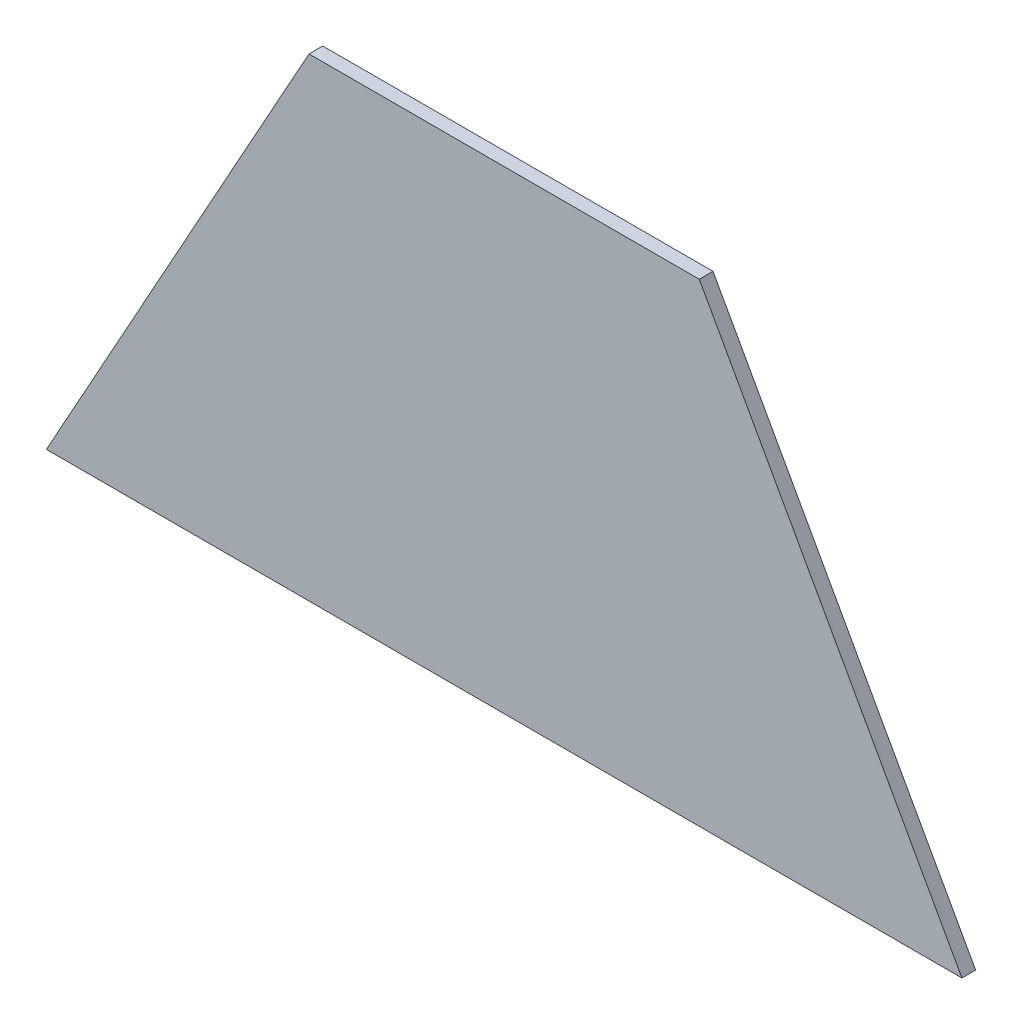
SolidWorks part; units mm, degrees
ref_plane "Front Plane" through (0, 0, 0) normal (0, 0, 1) x (1, 0, 0)
ref_plane "Top Plane" through (0, 0, 0) normal (0, 1, 0) x (1, 0, 0)
ref_plane "Right Plane" through (0, 0, 0) normal (1, 0, 0) x (0, 0, -1)
sketch "Sketch1" plane through (0, 0, 0) normal (0, 0, 1) x (1, 0, 0)
  line L0 (-592.8685, -14.2319) -> (626.3315, -14.2319)
  line L1 (-592.8685, -14.2319) -> (-243.1284, 616.716)
  line L2 (-243.1284, 616.716) -> (276.5914, 616.716)
  line L3 (276.5914, 616.716) -> (626.3315, -14.2319)
  dimension "D1" = 1219.2
  dimension "D2" = 61
  dimension "D3" = 61
  dimension "D4" = 519.7198
extrude "Boss-Extrude1" add sketch "Sketch1" along normal blind 18.2562
